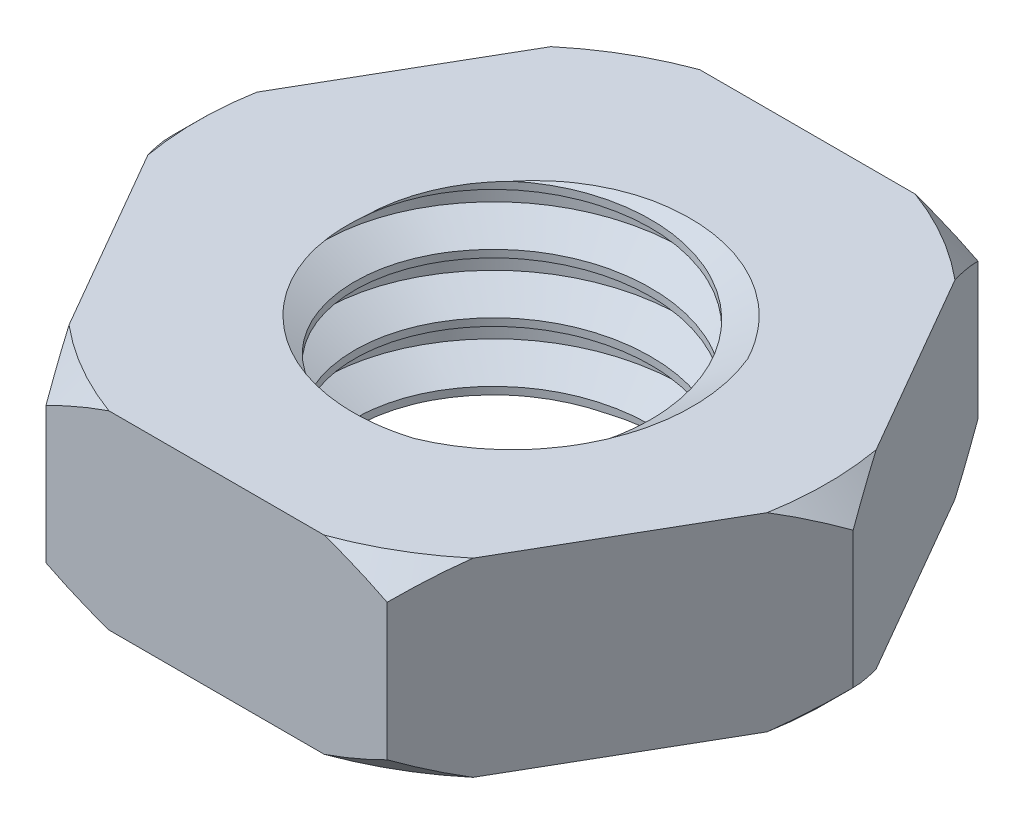
SolidWorks part; units mm, degrees
ref_plane "Front Plane" through (0, 0, 0) normal (0, 0, 1) x (1, 0, 0)
ref_plane "Top Plane" through (0, 0, 0) normal (0, 1, 0) x (1, 0, 0)
ref_plane "Right Plane" through (0, 0, 0) normal (1, 0, 0) x (0, 0, -1)
sketch "Sketch1" plane through (0, 0, 0) normal (0, 0, 1) x (1, 0, 0)
  line L0 (0, 0) -> (2.5, 0) construction
  line L1 (2.5, 0) -> (2.5, 3.2) construction
  line L2 (2.5, 3.2) -> (0, 3.2) construction
  line L3 (0, 3.2) -> (0, 0) construction
  line L4 (5.75, 2.75) -> (5.75, 0.45)
  line L5 (5.3, 0) -> (2.5, 0)
  line L6 (2.5, 0) -> (2.5, 3.2)
  line L7 (2.5, 3.2) -> (5.3, 3.2)
  line L8 (5.75, 0.45) -> (5.3, 0)
  line L9 (5.3, 3.2) -> (5.75, 2.75)
  point P3 (5.75, 3.2)
  point P6 (5.75, 0)
  dimension "D1" = 2.5
  dimension "D2" = 3.2
  dimension "D3" = 5.75
  dimension "D4" = 0.45
  dimension "D5" = 45
  dimension "D6" = 0.45
  dimension "D7" = 45
revolve "Revolve1" add sketch "Sketch1" angle 360 about L3
sketch "Sketch2" plane through (0, 3.2, 0) normal (0, 1, 0) x (1, 0, 0)
  line L1 (-2.875, 4.9796) -> (-5.75, 0)
  line L2 (-5.75, 0) -> (-2.875, -4.9796)
  line L3 (-2.875, -4.9796) -> (2.875, -4.9796)
  line L4 (2.875, -4.9796) -> (5.75, 0)
  line L5 (5.75, 0) -> (2.875, 4.9796)
  line L6 (2.875, 4.9796) -> (-2.875, 4.9796)
  circle A0 centre (0, 0) radius 4.9796 construction
  circle A2 centre (0, 0) radius 5.75 construction
  point P1 (0, 0)
extrude "Cut-Extrude1" cut sketch "Sketch2" against normal blind 10 flip side to cut
thread "Thread1" pitch 1 method cut profile "Thread Profile1" start angle 0, offset 1, length 0, pitch 1, diameter 5
ref_plane "Plane1" through (-2.5, 4.2, 0) normal (0, 0, -1) x (1, 0, 0)
sketch "Thread Profile1" plane through (-2.5, 4.2, 0) normal (0, 0, -1) x (1, 0, 0)
  line L0 (0, 0) -> (0, 1) construction
  line L11 (0, 0) -> (0, 0.875)
  line L12 (0, 0.875) -> (-0.5413, 0.5625)
  line L13 (-0.5413, 0.5625) -> (-0.5413, 0.3125)
  line L15 (-0.5413, 0.3125) -> (0, 0)
  line L17 (-0.5413, 0.4375) -> (0, 0.4375) construction
  point P2 (0, 0)
  dimension "Pitch" = 1
  dimension "Profile_Angle" = 60
  dimension "Profile_Land" = 0.25
  dimension "Profile_Height" = 0.5413
